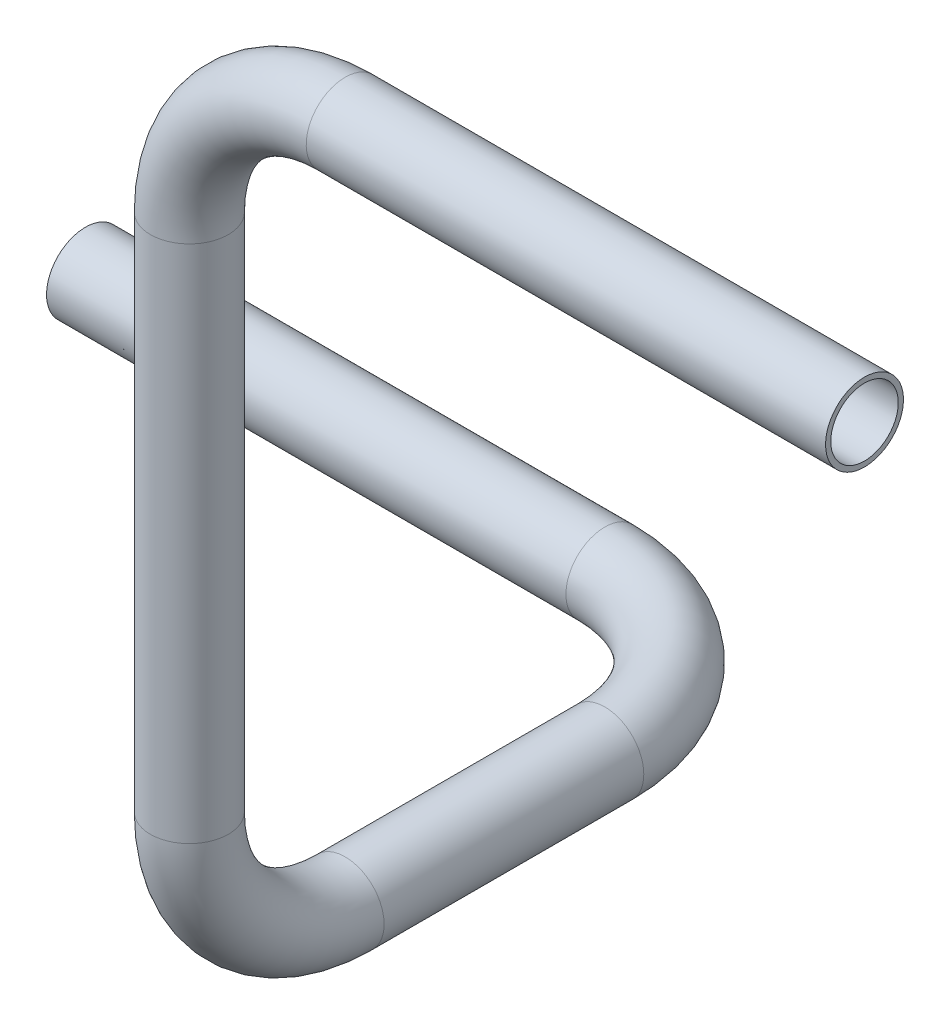
SolidWorks part; units mm, degrees
ref_plane "Front Plane" through (0, 0, 0) normal (0, 0, 1) x (1, 0, 0)
ref_plane "Top Plane" through (0, 0, 0) normal (0, 1, 0) x (1, 0, 0)
ref_plane "Right Plane" through (0, 0, 0) normal (1, 0, 0) x (0, 0, -1)
sketch3d "3DSketch1"
  line L0 (0, 0, 0) -> (200, 0, 0)
  line L1 (260, 0, -60) -> (260, 0, -160) construction
  line L2 (260, 60, -220) -> (260, 260, -220) construction
  line L3 (320, 320, -220) -> (520, 320, -220) construction
  line L4 (320, 320, 220) -> (520, 320, 220)
  line L5 (260, 60, 220) -> (260, 260, 220)
  line L6 (260, 0, 60) -> (260, 0, 160)
  arc A0 (200, 0, 0) -> (260, 0, -60) centre (200, 0, -60) ccw construction
  arc A1 (260, 0, -160) -> (260, 60, -220) centre (260, 60, -160) ccw construction
  arc A2 (260, 260, -220) -> (320, 320, -220) centre (320, 260, -220) ccw construction
  arc A3 (320, 320, 220) -> (260, 260, 220) centre (320, 260, 220) cw
  arc A4 (260, 60, 220) -> (260, 0, 160) centre (260, 60, 160) cw
  arc A5 (260, 0, 60) -> (200, 0, 0) centre (200, 0, 60) cw
  point P2 (260, 17.5736, -202.4264)
  point P4 (200, 60, -60)
  point P8 (320, 60, -160)
  point P12 (320, 260, -280)
  point P18 (320, 260, 280)
  point P22 (320, 60, 160)
  point P25 (200, 60, 60)
  point P27 (0, 0, 0)
  dimension "D2" = 60
  dimension "D4" = 60
  dimension "D6" = 60
  dimension "D1" = 200
  dimension "D3" = 100
  dimension "D5" = 200
  dimension "D7" = 200
sweep "Sweep-Thin1" add path "3DSketch1" circular profile diameter 30 parameters "D1"=2, "D3"=30
